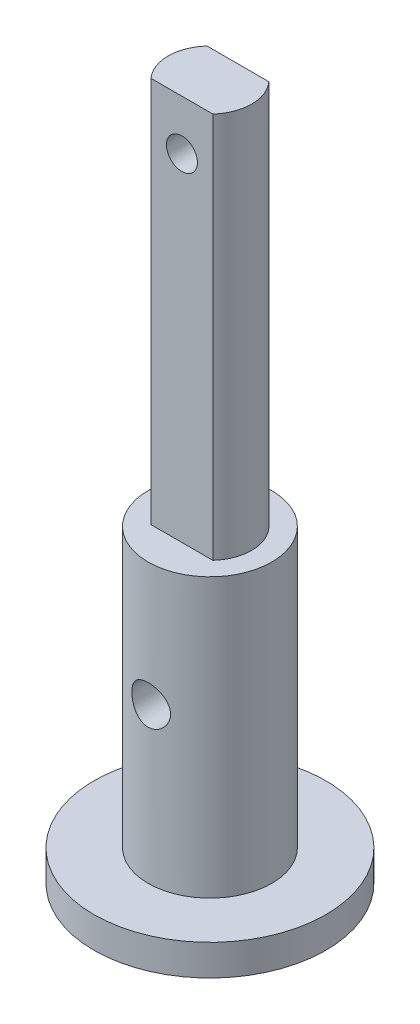
SolidWorks part; units mm, degrees
ref_plane "Front Plane" through (0, 0, 0) normal (0, 0, 1) x (1, 0, 0)
ref_plane "Top Plane" through (0, 0, 0) normal (0, 1, 0) x (1, 0, 0)
ref_plane "Right Plane" through (0, 0, 0) normal (1, 0, 0) x (0, 0, -1)
sketch "Sketch1" plane through (0, 0, 0) normal (0, 1, 0) x (1, 0, 0)
  circle A0 centre (0, 0) radius 7.5
  circle A1 centre (0, 0) radius 4
  dimension "D1" = 15
  dimension "D2" = 8
extrude "Boss-Extrude1" add sketch "Sketch1" along normal blind 2
extrude "Boss-Extrude2" add sketch "Sketch1<2>" along normal blind 45 contours A1 region at (0, 0, 0)
sketch "Sketch1<2>" plane through (0, 0, 0) normal (0, 1, 0) x (1, 0, 0) same geometry as "Sketch1"
sketch "Sketch2" plane through (0, 45, 0) normal (0, 1, 0) x (1, 0, 0)
  line L0 (-2, 1.8114) -> (2, 1.8114)
  line L1 (-3.8308, 0) -> (3.4281, 0) construction
  line L2 (-2, -1.8114) -> (2, -1.8114)
  arc A0 (-2, 1.8114) -> (-2, -1.8114) centre (0, 0) ccw
  arc A1 (2, -1.8114) -> (2, 1.8114) centre (0, 0) ccw
  circle A2 centre (0, 0) radius 4.5
extrude "Cut-Extrude1" cut sketch "Sketch2" against normal blind 25
sketch "Sketch3" plane through (0, 0, -1.8114) normal (0, 0, -1) x (-1, 0, 0)
  line L0 (0, 58.9249) -> (0, -1.0204) construction
  line L1 (4, 2) -> (-4, 2) construction
  circle A0 centre (0, 41.7782) radius 1
  circle A1 centre (0, 12) radius 1.25
  point P9 (0, 41.7782)
  dimension "D1" = 10
extrude "Cut-Extrude2" cut sketch "Sketch3" against normal blind 25 and the other way blind 25 contours A1 L0 | L0 A1 | L0 A0 | A0 L0 region at (-0.4244, 41.7782, -1.8114) region at (-0.5305, 12, -1.8114) region at (0.5305, 12, -1.8114) region at (0.4244, 41.7782, -1.8114)
